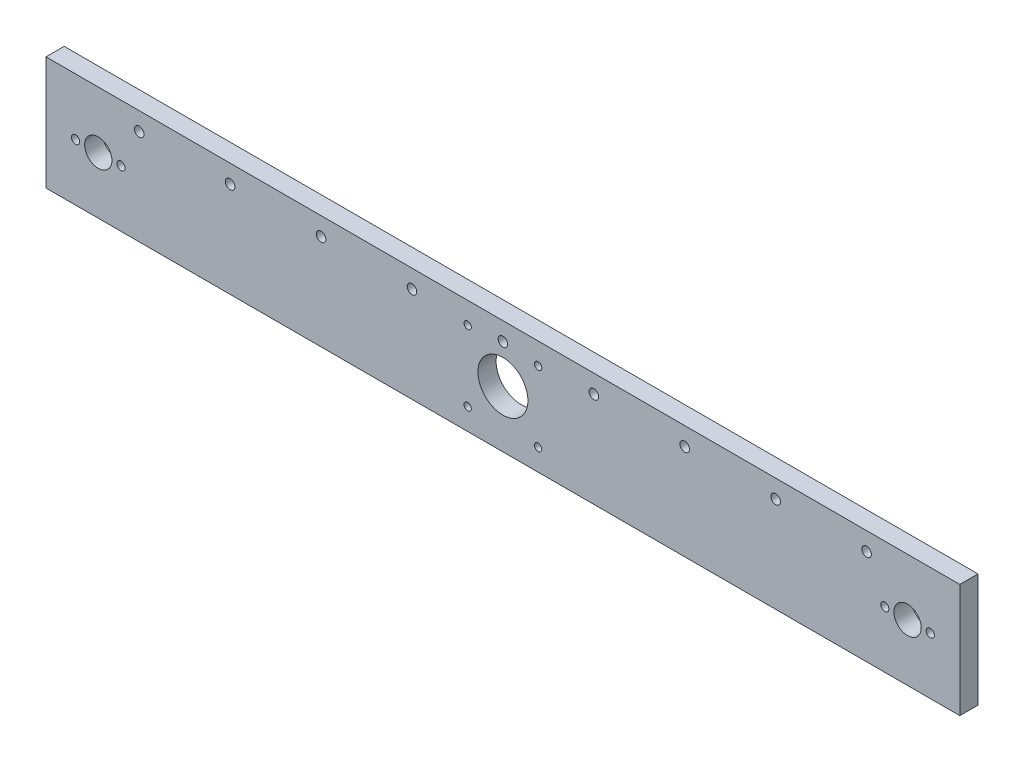
SolidWorks part; units mm, degrees
ref_plane "Front Plane" through (0, 0, 0) normal (0, 0, 1) x (1, 0, 0)
ref_plane "Top Plane" through (0, 0, 0) normal (0, 1, 0) x (1, 0, 0)
ref_plane "Right Plane" through (0, 0, 0) normal (1, 0, 0) x (0, 0, -1)
sketch "Sketch1" plane through (0, 0, 0) normal (0, 0, 1) x (1, 0, 0)
  line L0 (0, 0) -> (-200, 0) construction
  line L1 (-201, -25) -> (201, -25)
  line L2 (-201, -25) -> (-201, 25)
  line L3 (-201, 25) -> (201, 25)
  line L4 (201, -25) -> (201, 25)
  line L5 (-201, -25) -> (201, 25) construction
  line L6 (-201, 25) -> (201, -25) construction
  line L7 (0, 24) -> (0, -26) construction
  line L8 (-15.5, -15.5) -> (15.5, -15.5) construction
  line L9 (-15.5, -15.5) -> (-15.5, 15.5) construction
  line L10 (-15.5, 15.5) -> (15.5, 15.5) construction
  line L11 (15.5, -15.5) -> (15.5, 15.5) construction
  line L12 (-15.5, -15.5) -> (15.5, 15.5) construction
  line L13 (-15.5, 15.5) -> (15.5, -15.5) construction
  circle A0 centre (-178, 0) radius 6
  circle A1 centre (168, 0) radius 1.8
  circle A2 centre (0, 0) radius 11
  circle A3 centre (-188, 0) radius 1.8
  circle A4 centre (-168, 0) radius 1.8
  circle A5 centre (188, 0) radius 1.8
  circle A6 centre (178, 0) radius 6
  circle A7 centre (-15.5, 15.5) radius 1.6
  circle A8 centre (15.5, 15.5) radius 1.6
  circle A9 centre (-15.5, -15.5) radius 1.6
  circle A10 centre (15.5, -15.5) radius 1.6
  circle A11 centre (0, 17) radius 2.1
  circle A12 centre (40, 17) radius 2.1
  circle A13 centre (80, 17) radius 2.1
  circle A14 centre (120, 17) radius 2.1
  circle A15 centre (160, 17) radius 2.1
  circle A16 centre (-40, 17) radius 2.1
  circle A17 centre (-80, 17) radius 2.1
  circle A18 centre (-120, 17) radius 2.1
  circle A19 centre (-160, 17) radius 2.1
  point P0 (0, 0)
  dimension "D1" = 50
  dimension "D2" = 402
  dimension "D3" = 178
  dimension "D4" = 10
  dimension "D5" = 10
  dimension "D6" = 31
  dimension "D7" = 31
  dimension "D8" = 8
  dimension "D9" = 178
extrude "Boss-Extrude1" add sketch "Sketch1" along normal blind 8
